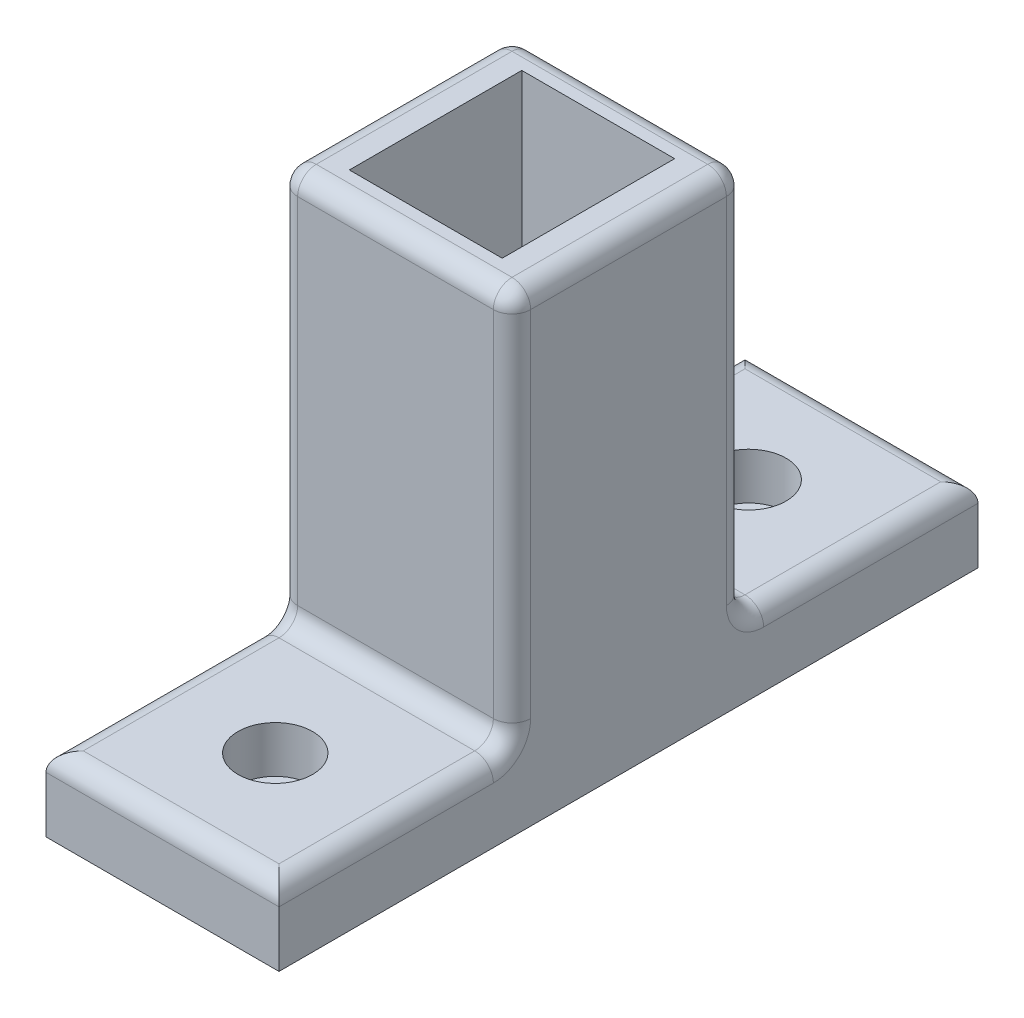
SolidWorks part; units mm, degrees
material "ABS"
ref_plane "Front Plane" through (0, 0, 0) normal (0, 0, 1) x (1, 0, 0)
ref_plane "Top Plane" through (0, 0, 0) normal (0, 1, 0) x (1, 0, 0)
ref_plane "Right Plane" through (0, 0, 0) normal (1, 0, 0) x (0, 0, -1)
sketch "Sketch1" plane through (0, 0, 0) normal (0, 1, 0) x (1, 0, 0)
  line L1 (-8.2, -9.25) -> (8.2, -9.25)
  line L2 (-8.2, -9.25) -> (-8.2, 9.25)
  line L3 (-8.2, 9.25) -> (8.2, 9.25)
  line L4 (8.2, -9.25) -> (8.2, 9.25)
  line L5 (-8.2, -9.25) -> (8.2, 9.25) construction
  line L6 (-8.2, 9.25) -> (8.2, -9.25) construction
  line L7 (-12.5, -12.5) -> (12.5, -12.5)
  line L8 (-12.5, -12.5) -> (-12.5, 12.5)
  line L9 (-12.5, 12.5) -> (12.5, 12.5)
  line L10 (12.5, -12.5) -> (12.5, 12.5)
  line L11 (-12.5, -12.5) -> (12.5, 12.5) construction
  line L12 (-12.5, 12.5) -> (12.5, -12.5) construction
  point P0 (0, 0)
  point P6 (0, 0)
  dimension "D1" = 16.4
  dimension "D2" = 18.5
  dimension "D3" = 25
  dimension "D4" = 25
extrude "Boss-Extrude1" add sketch "Sketch1" along normal blind 50
sketch "Sketch6" plane through (0, 0, 0) normal (0, 1, 0) x (1, 0, 0)
  line L13 (-12.5, -37.5) -> (12.5, -37.5)
  line L14 (-12.5, -37.5) -> (-12.5, 37.5)
  line L15 (-12.5, 37.5) -> (12.5, 37.5)
  line L16 (12.5, -37.5) -> (12.5, 37.5)
  line L17 (-12.5, -37.5) -> (12.5, 37.5) construction
  line L18 (-12.5, 37.5) -> (12.5, -37.5) construction
  point P4 (0, 0)
  dimension "D5" = 75
  dimension "D6" = 25
extrude "Boss-Extrude3" add sketch "Sketch6" along normal blind 8
fillet "Fillet2" radius 2 16 edges at (0, 8, -12.5) (0, 50, -12.5) (12.5, 29, -12.5) (12.5, 50, 0) (12.5, 29, 12.5) (-12.5, 29, 12.5) (0, 50, 12.5) (-12.5, 29, -12.5) (-12.5, 50, 0) (-12.5, 8, -25) (12.5, 8, -25) (0, 8, -37.5) (0, 8, 37.5) (-12.5, 8, 25) (0, 8, 12.5) (12.5, 8, 25)
sketch "Sketch7" plane through (0, 8, 0) normal (0, 1, 0) x (1, 0, 0)
  line L0 (0, 0) -> (0, 25.4) construction
  line L1 (0, 0) -> (0, -25.4) construction
  circle A0 centre (0, 0) radius 4
  circle A1 centre (0, 25.4) radius 4
  circle A2 centre (0, -25.4) radius 4
extrude "Cut-Extrude1" cut sketch "Sketch7" against normal blind 5
sketch "Sketch8" plane through (0, 0, 0) normal (0, 1, 0) x (1, 0, 0)
  line L0 (0, 0) -> (0, 25.4) construction
  line L1 (0, 0) -> (0, -25.4) construction
  circle A0 centre (0, 0) radius 2.3813
  circle A1 centre (0, 25.4) radius 2.3813
  circle A2 centre (0, -25.4) radius 2.3813
extrude "Cut-Extrude4" cut sketch "Sketch8" against normal through all and the other way through all
